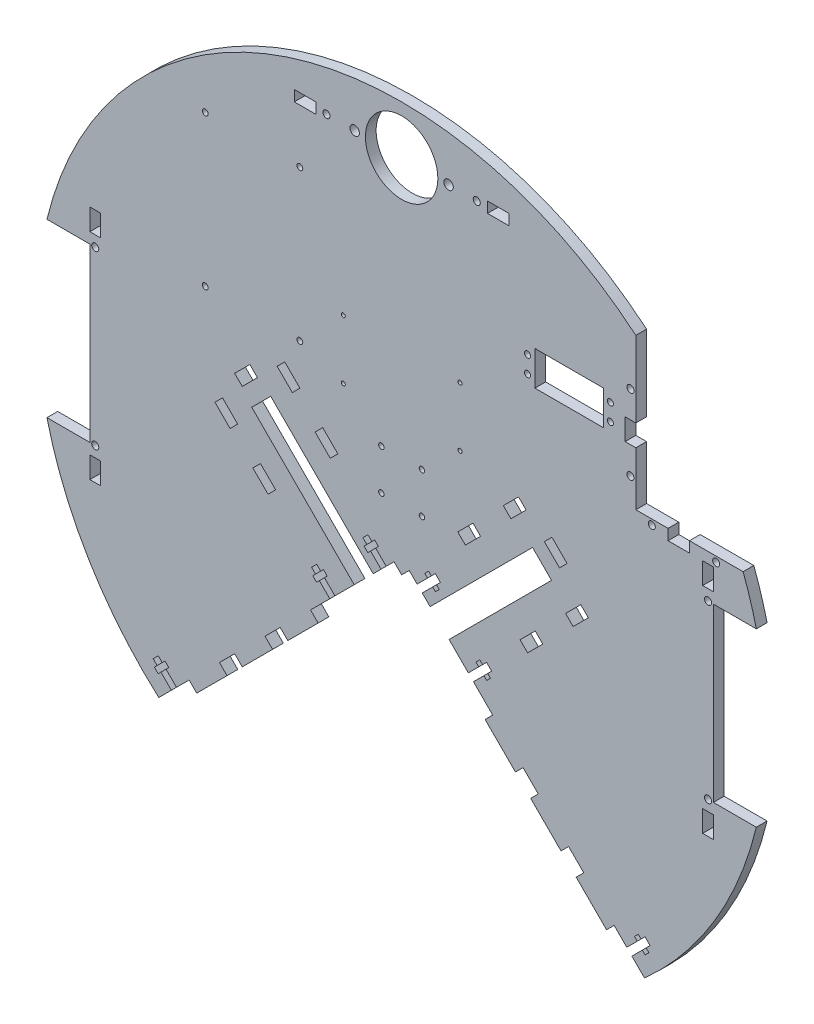
SolidWorks part; units mm, degrees
ref_plane "Front Plane" through (0, 0, 0) normal (0, 0, 1) x (1, 0, 0)
ref_plane "Top Plane" through (0, 0, 0) normal (0, 1, 0) x (1, 0, 0)
ref_plane "Right Plane" through (0, 0, 0) normal (1, 0, 0) x (0, 0, -1)
sketch "Sketch1" plane through (0, 0, 0) normal (0, 0, 1) x (1, 0, 0)
  circle A0 centre (0, 0) radius 215.9
  dimension "D1" = 431.8
extrude "Base Plate Extrusion" add sketch "Sketch1" along normal blind 6.35
sketch "Sketch2" plane through (0, 0, 6.35) normal (0, 0, 1) x (1, 0, 0)
  line L0 (0, 0) -> (0, -230.9791) construction
  line L1 (0, -17.4608) -> (143.6841, -161.1449)
  line L2 (0, -17.4608) -> (-143.6841, -161.1449)
  circle A1 centre (0, 0) radius 215.9 construction
  arc A2 (143.6841, -161.1449) -> (-143.6841, -161.1449) centre (0, 0) cw
  dimension "D1" = 90
  dimension "D2" = 203.2
extrude "V Funnel Cut" cut sketch "Sketch2" against normal through all
sketch "Sketch3" plane through (0, 0, 6.35) normal (0, 0, 1) x (1, 0, 0)
  line L0 (0, 0) -> (251.7982, 0) construction
  line L1 (209.8384, 50.8) -> (184.4384, 50.8)
  line L2 (209.8384, 50.8) -> (209.8384, -50.8)
  line L3 (209.8384, -50.8) -> (184.4384, -50.8)
  line L4 (184.4384, 50.8) -> (184.4384, -50.8)
  arc A0 (143.6841, -161.1449) -> (-143.6841, -161.1449) centre (0, 0) ccw construction
  arc A1 (209.8384, 50.8) -> (209.8384, -50.8) centre (0, 0) cw
  arc M7 (143.6841, -161.1449) -> (-143.6841, -161.1449) centre (0, 0) ccw
  dimension "D1" = 25.4
  dimension "D2" = 101.6
extrude "Wheel Track Cut" cut sketch "Sketch3" against normal through all contours L2 L0 A1 | L4 L0 L2 L1 | L0 L4 L3 L2 | L0 L2 M7 region at (197.1384, 25.4, 6.35) region at (197.1384, -25.4, 6.35) region at (212.266, 19.0862, 6.35) region at (212.266, -19.0862, 6.35)
mirror "Wheel Track Cut Mirror" about plane through (0, 0, 0) normal (1, 0, 0) of "Wheel Track Cut"
sketch "Sketch4" plane through (0, 0, 6.35) normal (0, 0, 1) x (1, 0, 0)
  line L0 (88.68, 15.0926) -> (77.4547, 26.3179)
  line L1 (88.68, 15.0926) -> (28.0633, -45.5241)
  line L2 (77.4547, 26.3179) -> (16.838, -34.2988)
  line L3 (28.0633, -45.5241) -> (16.838, -34.2988)
  line L4 (84.3174, 21.9553) -> (56.956, -5.4061) construction
  line L5 (65.1069, -1.7454) -> (69.5826, 2.7303) construction
  line L6 (65.0924, 7.2204) -> (60.6167, 2.7447) construction
  line L7 (143.6841, -161.1449) -> (0, -17.4608) construction
  dimension "D1" = 15.875
  dimension "D2" = 85.725
extrude "Cut-Extrude3" cut sketch "Sketch4" against normal through all
sketch "Sketch5" plane through (0, 0, 6.35) normal (0, 0, 1) x (1, 0, 0)
  line L0 (-4.4901, -21.951) -> (0, -17.4608)
  line L1 (-4.4901, -21.951) -> (0, -26.4411)
  line L2 (0, -17.4608) -> (4.4901, -21.951)
  line L3 (0, -26.4411) -> (4.4901, -21.951)
  line L4 (0, -17.4608) -> (-143.6841, -161.1449) construction
  line L6 (4.4901, -21.951) -> (0, -26.4411) construction
  dimension "D1" = 6.35
extrude "Boss-Extrude2" add sketch "Sketch5" against normal up to surface (6.35 mm away) up to face at (14.0691, -14.8765, 0)
mirror "Mirror2" about plane through (0, 0, 0) normal (1, 0, 0) of "Cut-Extrude3"
sketch "Sketch6" plane through (8.7304, -8.7304, 0) normal (0.7071, -0.7071, 0) x (0, 0, -1)
  line L0 (-6.35, -52.0342) -> (-6.35, -215.5467) construction
  line L1 (-6.35, -190.1467) -> (0, -190.1467)
  line L2 (-6.35, -190.1467) -> (-6.35, -164.7467)
  line L3 (-6.35, -164.7467) -> (0, -164.7467)
  line L4 (0, -190.1467) -> (0, -164.7467)
  line L5 (0, -52.0342) -> (0, -215.5467) construction
  dimension "D1" = 25.4
  dimension "D2" = 25.4
extrude "Boss-Extrude3" add sketch "Sketch6" along normal blind 6.35
pattern_linear "LPattern1" count 3 spacing 38.1 along (0.7071, 0.7071, 0) of "Boss-Extrude3"
sketch "Sketch7" plane through (-8.7304, -8.7304, 0) normal (-0.7071, -0.7071, 0) x (0, 0, 1)
  line L0 (6.35, -215.5467) -> (6.35, -52.0342) construction
  line L1 (6.35, -164.7467) -> (0, -164.7467)
  line L2 (6.35, -164.7467) -> (6.35, -190.1467)
  line L3 (6.35, -190.1467) -> (0, -190.1467)
  line L4 (0, -164.7467) -> (0, -190.1467)
  line L5 (0, -215.5467) -> (0, -52.0342) construction
  dimension "D1" = 25.4
  dimension "D2" = 25.4
extrude "Boss-Extrude4" add sketch "Sketch7" along normal blind 6.35
pattern_linear "LPattern2" count 3 spacing 38.1 along (-0.7071, 0.7071, 0) of "Boss-Extrude4"
sketch "Sketch8" plane through (0, 0, 0) normal (0, 0, -1) x (-1, 0, 0)
  line L0 (-70.046, -24.645) -> (-79.0263, -15.6648)
  line L1 (-79.0263, -15.6648) -> (-83.5164, -20.1549)
  line L2 (-83.5164, -20.1549) -> (-74.5361, -29.1352)
  line L3 (-74.5361, -29.1352) -> (-70.046, -24.645)
  line L4 (-96.9868, 2.2957) -> (-101.4769, -2.1944)
  line L5 (-101.4769, -2.1944) -> (-110.4572, 6.7859)
  line L6 (-110.4572, 6.7859) -> (-105.967, 11.276)
  line L7 (-105.967, 11.276) -> (-96.9868, 2.2957)
  line L8 (-97.8965, 28.3267) -> (-88.9163, 37.307)
  line L9 (-88.9163, 37.307) -> (-84.4262, 32.8169)
  line L10 (-84.4262, 32.8169) -> (-93.4064, 23.8366)
  line L11 (-93.4064, 23.8366) -> (-97.8965, 28.3267)
  line L12 (-64.6578, 34.6246) -> (-60.1677, 39.1148)
  line L13 (-60.1677, 39.1148) -> (-69.148, 48.095)
  line L14 (-69.148, 48.095) -> (-73.6381, 43.6049)
  line L15 (-73.6381, 43.6049) -> (-64.6578, 34.6246)
  line L16 (-46.6973, 16.6641) -> (-42.2072, 21.1543)
  line L17 (-42.2072, 21.1543) -> (-33.2269, 12.174)
  line L18 (-33.2269, 12.174) -> (-37.7171, 7.6839)
  line L19 (-37.7171, 7.6839) -> (-46.6973, 16.6641)
  line L20 (-105.967, 11.276) -> (-110.4572, 6.7859) construction
  line L21 (-69.148, 48.095) -> (-73.6381, 43.6049) construction
extrude "Cut-Extrude4" cut sketch "Sketch8" against normal blind 6.35
sketch "Sketch9" plane through (0, 0, 0) normal (0, 0, -1) x (-1, 0, 0)
  line L0 (-138.5621, 165.5698) -> (-138.5621, 76.2)
  line L1 (-138.5621, 76.2) -> (-202.0059, 76.2)
  line L2 (-132.2121, 76.2) -> (-145.8628, 76.2) construction
  line L3 (-138.5621, 152.4) -> (-138.5621, 138.6586) construction
  arc A0 (209.8384, 50.8) -> (-209.8384, 50.8) centre (0, 0) ccw construction
  arc A1 (-202.0059, 76.2) -> (-138.5621, 165.5698) centre (0, 0) cw
extrude "Cut-Extrude5" cut sketch "Sketch9" against normal through all
sketch "Sketch10" plane through (0, 0, 0) normal (0, 0, -1) x (-1, 0, 0)
  line L0 (51.1875, 21.1543) -> (42.2072, 12.174)
  line L1 (42.2072, 12.174) -> (37.7171, 16.6641)
  line L2 (37.7171, 16.6641) -> (46.6973, 25.6444)
  line L3 (46.6973, 25.6444) -> (51.1875, 21.1543)
  line L4 (64.6578, 34.6246) -> (60.1677, 39.1148)
  line L5 (60.1677, 39.1148) -> (69.148, 48.095)
  line L6 (69.148, 48.095) -> (73.6381, 43.6049)
  line L7 (73.6381, 43.6049) -> (64.6578, 34.6246)
  line L8 (89.8026, 36.4207) -> (85.3124, 31.9306)
  line L9 (85.3124, 31.9306) -> (94.2927, 22.9503)
  line L10 (94.2927, 22.9503) -> (98.7828, 27.4404)
  line L11 (98.7828, 27.4404) -> (89.8026, 36.4207)
  line L12 (105.967, 11.276) -> (96.9868, 2.2957)
  line L13 (96.9868, 2.2957) -> (101.4769, -2.1944)
  line L14 (101.4769, -2.1944) -> (110.4572, 6.7859)
  line L15 (110.4572, 6.7859) -> (105.967, 11.276)
  line L16 (88.0065, -15.6648) -> (83.5164, -11.1747)
  line L17 (83.5164, -11.1747) -> (74.5361, -20.1549)
  line L18 (74.5361, -20.1549) -> (79.0263, -24.645)
  line L19 (79.0263, -24.645) -> (88.0065, -15.6648)
  line L20 (37.7171, 16.6641) -> (42.2072, 12.174) construction
  line L21 (74.5361, -20.1549) -> (79.0263, -24.645) construction
extrude "Cut-Extrude6" cut sketch "Sketch10" against normal blind 6.35
sketch "Sketch11" plane through (0, 0, 0) normal (0, 0, -1) x (-1, 0, 0)
  line L1 (184.4384, -69.85) -> (178.0884, -69.85)
  line L2 (184.4384, -69.85) -> (184.4384, -57.15)
  line L3 (184.4384, -57.15) -> (178.0884, -57.15)
  line L4 (178.0884, -69.85) -> (178.0884, -57.15)
  line L5 (184.4384, 57.15) -> (178.0884, 57.15)
  line L6 (184.4384, 57.15) -> (184.4384, 69.85)
  line L7 (184.4384, 69.85) -> (178.0884, 69.85)
  line L8 (178.0884, 57.15) -> (178.0884, 69.85)
  line L9 (-178.0884, -69.85) -> (-184.4384, -69.85)
  line L10 (-178.0884, -69.85) -> (-178.0884, -57.15)
  line L11 (-178.0884, -57.15) -> (-184.4384, -57.15)
  line L12 (-184.4384, -69.85) -> (-184.4384, -57.15)
  line L13 (-178.0884, 57.15) -> (-184.4384, 57.15)
  line L14 (-178.0884, 57.15) -> (-178.0884, 69.85)
  line L15 (-178.0884, 69.85) -> (-184.4384, 69.85)
  line L16 (-184.4384, 57.15) -> (-184.4384, 69.85)
extrude "Cut-Extrude7" cut sketch "Sketch11" against normal blind 6.35
sketch "Sketch12" plane through (0, 0, 0) normal (0, 0, -1) x (-1, 0, 0)
  line L0 (-202.0059, 76.2) -> (-138.5621, 76.2) construction
  line L1 (-157.6121, 69.85) -> (-170.284, 69.85)
  line L2 (-157.6121, 69.85) -> (-157.6121, 76.2)
  line L3 (-157.6121, 76.2) -> (-170.284, 76.2)
  line L4 (-170.284, 69.85) -> (-170.284, 76.2)
  line L5 (-138.5621, 76.2) -> (-138.5621, 165.5698) construction
  line L6 (-132.2121, 120.65) -> (-138.5621, 120.65)
  line L7 (-132.2121, 120.65) -> (-132.2121, 107.95)
  line L8 (-132.2121, 107.95) -> (-138.5621, 107.95)
  line L9 (-138.5621, 120.65) -> (-138.5621, 107.95)
  line L10 (-138.5621, 107.95) -> (-132.2121, 107.95) construction
extrude "Cut-Extrude8" cut sketch "Sketch12" against normal blind 6.35
sketch "Sketch13" plane through (0, 0, 6.35) normal (0, 0, 1) x (1, 0, 0)
  circle A0 centre (0, 187.325) radius 21.4313
  circle A1 centre (27.7812, 187.325) radius 2.7781
  circle A2 centre (-27.7813, 187.325) radius 2.7781
  dimension "D1" = 42.8625
  dimension "D2" = 5.5562
extrude "Cut-Extrude9" cut sketch "Sketch13" against normal through all
sketch "Sketch14" plane through (0, 0, 6.35) normal (0, 0, 1) x (1, 0, 0)
  line L0 (184.4384, 48.6664) -> (178.0884, 52.9336) construction
  line L1 (184.4384, 50.8) -> (184.4384, -50.8) construction
  line L2 (178.0884, 48.6664) -> (184.4384, 48.6664) construction
  line L3 (184.4384, 52.9336) -> (178.0884, 48.6664) construction
  line L4 (184.4384, -52.9336) -> (178.0884, -48.6664) construction
  line L5 (184.4384, -48.6664) -> (178.0884, -52.9336) construction
  line L6 (178.0884, -48.6664) -> (184.4384, -48.6664) construction
  circle A0 centre (181.2634, 50.8) radius 2.0955
  circle A1 centre (181.2634, -50.8) radius 2.0955
  dimension "D1" = 4.191
extrude "Cut-Extrude10" cut sketch "Sketch14" against normal through all
mirror "Mirror3" about plane through (0, 0, 0) normal (1, 0, 0) of "Cut-Extrude10"
sketch "Sketch15" plane through (0, 0, 6.35) normal (0, 0, 1) x (1, 0, 0)
  line L0 (-134.7038, -152.1647) -> (-152.6084, -134.2601) construction
  line L1 (-125.7236, -143.1844) -> (-143.6841, -161.1449) construction
  line L2 (-40.9724, -58.4333) -> (-60.7132, -38.6924) construction
  line L3 (-28.0633, -45.5241) -> (-53.8815, -71.3424) construction
  line L4 (-10.6641, -28.1249) -> (-27.2834, -11.5055) construction
  line L5 (-4.4901, -21.951) -> (-16.838, -34.2988) construction
  line B0 (-136.2125, -153.6734) -> (-133.1952, -150.656)
  line B1 (-141.6366, -142.2146) -> (-140.0022, -140.5801)
  line B2 (-140.0022, -140.5801) -> (-137.7571, -142.8252)
  line B3 (-137.7571, -142.8252) -> (-139.3915, -144.4596)
  line B4 (-139.3915, -144.4596) -> (-133.1952, -150.656)
  line B5 (-141.6366, -142.2146) -> (-143.9715, -139.8797)
  line B6 (-143.9715, -139.8797) -> (-146.9888, -142.8971)
  line B7 (-144.654, -145.2319) -> (-146.9888, -142.8971)
  line B8 (-142.4089, -147.477) -> (-136.2125, -153.6734)
  line B9 (-144.0433, -149.1114) -> (-142.4089, -147.477)
  line B10 (-146.2884, -146.8663) -> (-144.0433, -149.1114)
  line B11 (-144.654, -145.2319) -> (-146.2884, -146.8663)
  line B12 (-42.4811, -59.9419) -> (-39.4637, -56.9246)
  line B13 (-47.9052, -48.4831) -> (-46.2708, -46.8487)
  line B14 (-46.2708, -46.8487) -> (-44.0257, -49.0938)
  line B15 (-44.0257, -49.0938) -> (-45.6601, -50.7282)
  line B16 (-45.6601, -50.7282) -> (-39.4637, -56.9246)
  line B17 (-47.9052, -48.4831) -> (-50.24, -46.1483)
  line B18 (-50.24, -46.1483) -> (-53.2574, -49.1656)
  line B19 (-50.9225, -51.5005) -> (-53.2574, -49.1656)
  line B20 (-48.6775, -53.7456) -> (-42.4811, -59.9419)
  line B21 (-50.3119, -55.38) -> (-48.6775, -53.7456)
  line B22 (-52.5569, -53.1349) -> (-50.3119, -55.38)
  line B23 (-50.9225, -51.5005) -> (-52.5569, -53.1349)
  line B24 (-12.1727, -29.6336) -> (-9.1554, -26.6162)
  line B25 (-17.5968, -18.1748) -> (-15.9624, -16.5404)
  line B26 (-15.9624, -16.5404) -> (-13.7173, -18.7854)
  line B27 (-13.7173, -18.7854) -> (-15.3517, -20.4198)
  line B28 (-15.3517, -20.4198) -> (-9.1554, -26.6162)
  line B29 (-17.5968, -18.1748) -> (-19.9317, -15.8399)
  line B30 (-19.9317, -15.8399) -> (-22.949, -18.8573)
  line B31 (-20.6142, -21.1921) -> (-22.949, -18.8573)
  line B32 (-18.3691, -23.4372) -> (-12.1727, -29.6336)
  line B33 (-20.0035, -25.0716) -> (-18.3691, -23.4372)
  line B34 (-22.2486, -22.8265) -> (-20.0035, -25.0716)
  line B35 (-20.6142, -21.1921) -> (-22.2486, -22.8265)
sketch_block_instance "TSlot-1"
sketch_block "TSlot" parameters "D1"=3.302, "D2"=3.175
sketch_block_instance "TSlot-3"
sketch_block_instance "TSlot-4"
extrude "Cut-Extrude11" cut sketch "Sketch15" against normal through all
mirror "Mirror4" about plane through (0, 0, 0) normal (1, 0, 0) of "Cut-Extrude11"
sketch "Sketch16" plane through (0, 0, 6.35) normal (0, 0, 1) x (1, 0, 0)
  line L0 (0, 0) -> (0, 33.3041) construction
  line L1 (-12, 9.525) -> (12, 9.525) construction
  line L2 (-12, 9.525) -> (-12, 33.525) construction
  line L3 (-12, 33.525) -> (12, 33.525) construction
  line L4 (12, 9.525) -> (12, 33.525) construction
  line L5 (-12, 9.525) -> (12, 33.525) construction
  line L6 (-12, 33.525) -> (12, 9.525) construction
  circle A0 centre (-12, 33.525) radius 1.6
  circle A1 centre (12, 33.525) radius 1.6
  circle A2 centre (12, 9.525) radius 1.6
  circle A3 centre (-12, 9.525) radius 1.6
  point P0 (0, 21.525)
  dimension "D2" = 3.2
  dimension "D1" = 24
  dimension "D3" = 9.525
extrude "Gyro Holes" cut sketch "Sketch16" against normal through all
sketch "Sketch17" plane through (0, 0, 6.35) normal (0, 0, 1) x (1, 0, 0)
  circle A0 centre (-34.5281, 89.2969) radius 1.1906
  circle A1 centre (34.5281, 89.2969) radius 1.1906
  circle A2 centre (34.5281, 54.3719) radius 1.1906
  circle A3 centre (-34.5281, 54.3719) radius 1.1906
  circle A6 centre (-34.5281, 54.3719) radius 1.1906 construction
extrude "Motor Driver Holes" cut sketch "Sketch17" against normal through all
sketch "Sketch18" plane through (0, 0, 6.35) normal (0, 0, 1) x (1, 0, 0)
  circle A0 centre (-116.1664, 152.381) radius 1.7145
  circle A1 centre (-60.2039, 152.381) radius 1.7145
  circle A2 centre (-60.2039, 63.3159) radius 1.7145
  circle A3 centre (-116.1664, 63.3159) radius 1.7145
  dimension "D1" = 3.429
extrude "Teensy Board Holes" cut sketch "Sketch18" against normal through all
sketch "Sketch19" plane through (0, 0, 6.35) normal (0, 0, 1) x (1, 0, 0)
  line L0 (46.5836, 190.5) -> (42.3164, 184.15) construction
  line L1 (46.5836, 184.15) -> (42.3164, 190.5) construction
  line L2 (-42.3164, 190.5) -> (-46.5836, 184.15) construction
  line L3 (-42.3164, 184.15) -> (-46.5836, 190.5) construction
  circle A0 centre (44.45, 187.325) radius 2.0955
  circle A1 centre (-44.45, 187.325) radius 2.0955
  dimension "D1" = 4.191
extrude "Cut-Extrude15" cut sketch "Sketch19" against normal through all
sketch "Sketch20" plane through (0, 0, 0) normal (0, 0, -1) x (-1, 0, 0)
  line L1 (-50.8, 184.15) -> (-63.5, 184.15)
  line L2 (-50.8, 184.15) -> (-50.8, 190.5)
  line L3 (-50.8, 190.5) -> (-63.5, 190.5)
  line L4 (-63.5, 184.15) -> (-63.5, 190.5)
  line L5 (63.5, 184.15) -> (50.8, 184.15)
  line L6 (63.5, 184.15) -> (63.5, 190.5)
  line L7 (63.5, 190.5) -> (50.8, 190.5)
  line L8 (50.8, 184.15) -> (50.8, 190.5)
extrude "Cut-Extrude16" cut sketch "Sketch20" against normal through all
sketch "Sketch21" plane through (0, 0, 6.35) normal (0, 0, 1) x (1, 0, 0)
  line L0 (132.2121, 134.3914) -> (138.5621, 138.6586) construction
  line L1 (138.5621, 120.65) -> (138.5621, 165.5698) construction
  line L2 (132.2121, 138.6586) -> (138.5621, 138.6586) construction
  line L3 (132.2121, 138.6586) -> (138.5621, 134.3914) construction
  line L4 (132.2121, 94.0187) -> (138.5621, 89.7515) construction
  line L5 (138.5621, 76.2) -> (138.5621, 107.95) construction
  line L6 (132.2121, 89.7515) -> (138.5621, 94.0187) construction
  line L7 (145.8628, 69.85) -> (150.13, 76.2) construction
  line L8 (157.6121, 76.2) -> (138.5621, 76.2) construction
  line L9 (150.13, 69.85) -> (150.13, 76.2) construction
  line L10 (150.13, 69.85) -> (145.8628, 76.2) construction
  line L11 (145.8628, 69.85) -> (145.8628, 76.2) construction
  line L12 (188.2134, 69.85) -> (183.9462, 76.2) construction
  line L13 (202.0059, 76.2) -> (170.284, 76.2) construction
  circle A0 centre (186.0798, 73.025) radius 2.0955
  circle A1 centre (147.9964, 73.025) radius 2.0955
  circle A2 centre (135.3871, 91.8851) radius 2.0955
  circle A3 centre (135.3871, 136.525) radius 2.0955
  dimension "D1" = 4.191
extrude "Cut-Extrude17" cut sketch "Sketch21" against normal blind 6.35
sketch "Sketch24" plane through (0, 0, 0) normal (0, 0, -1) x (-1, 0, 0)
  line L1 (-119.4865, 108.6527) -> (-78.8465, 108.6527)
  line L2 (-119.4865, 108.6527) -> (-119.4865, 128.9727)
  line L3 (-119.4865, 128.9727) -> (-78.8465, 128.9727)
  line L4 (-78.8465, 108.6527) -> (-78.8465, 128.9727)
  dimension "D1" = 20.32
  dimension "D2" = 40.64
extrude "Cut-Extrude18" cut sketch "Sketch24" against normal blind 6.35
sketch "Sketch25" plane through (0, 0, 0) normal (0, 0, -1) x (-1, 0, 0)
  circle A0 centre (-123.476, 123.6857) radius 1.778
  circle A1 centre (-123.476, 113.6857) radius 1.778
  circle A2 centre (-74.476, 123.6857) radius 1.778
  circle A3 centre (-74.476, 113.6857) radius 1.778
extrude "Cut-Extrude19" cut sketch "Sketch25" against normal blind 6.35
